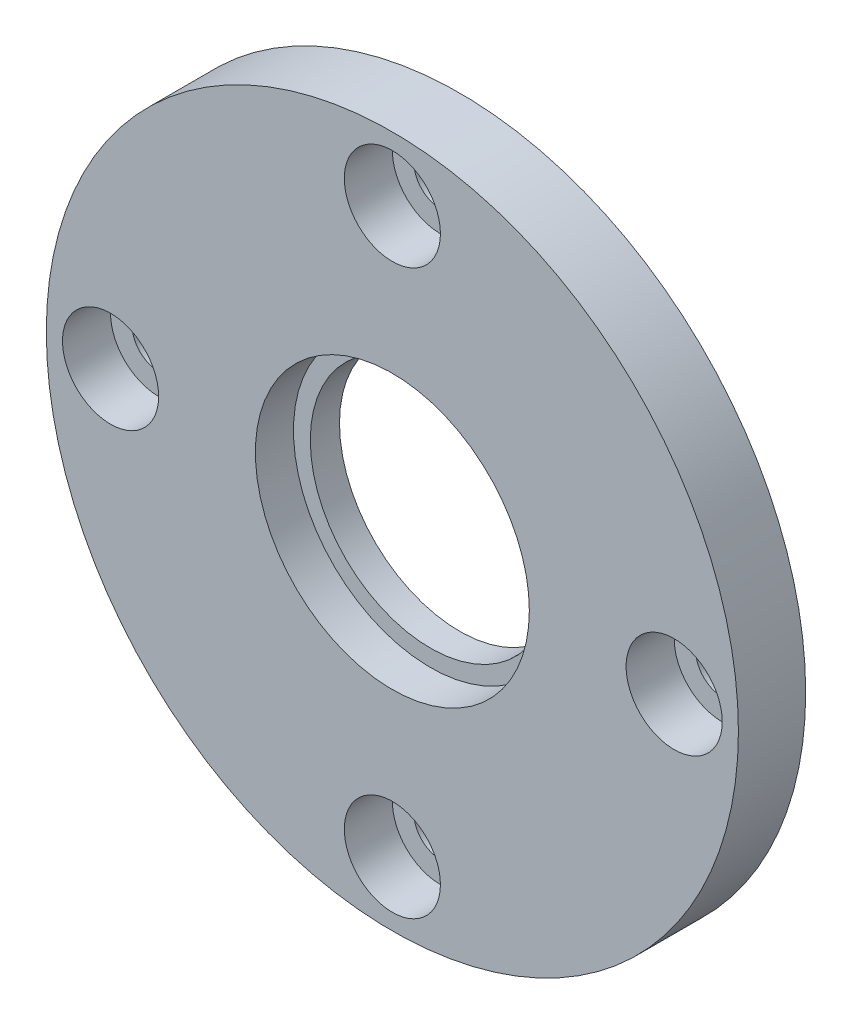
SolidWorks part; units mm, degrees
ref_plane "Front Plane" through (0, 0, 0) normal (0, 0, 1) x (1, 0, 0)
ref_plane "Top Plane" through (0, 0, 0) normal (0, 1, 0) x (1, 0, 0)
ref_plane "Right Plane" through (0, 0, 0) normal (1, 0, 0) x (0, 0, -1)
sketch "Sketch1" plane through (0, 0, 0) normal (1, 0, 0) x (0, 0, -1)
  line L0 (-114.9, -9.5) -> (-144, -9.5)
  line L5 (-1000, 0) -> (49000, 0)
  line L6 (0, -9.5) -> (0, 9.5)
  line L13 (0, 9.5) -> (-53.3, 9.5)
  line L26 (-53.3, 9.5) -> (-53.3, 14)
  line L27 (-53.3, 14) -> (-114.9, 14)
  line L32 (-114.9, 14) -> (-114.9, 9.5)
  line L34 (-160, 7) -> (-160, -7)
  line L36 (-114.9, -9.5) -> (-114.9, -14)
  line L37 (-114.9, -14) -> (-53.3, -14)
  line L38 (-53.3, -14) -> (-53.3, -9.5)
  line L39 (0, -9.5) -> (-53.3, -9.5)
  line L40 (-21.7, 36) -> (-14.7, 36)
  line L41 (-131.5, 22.6312) -> (-114.9, 22.6312)
  line L42 (-131.5, 22.6312) -> (-131.5, -22.6312)
  line L43 (-131.5, -22.6312) -> (-114.9, -22.6312)
  line L44 (-114.9, 22.6312) -> (-114.9, -22.6312)
  line L45 (-131.5, 22.6312) -> (-114.9, -22.6312) construction
  line L46 (-131.5, -22.6312) -> (-114.9, 22.6312) construction
  line L47 (-36.7, 22.6312) -> (-53.3, 22.6312)
  line L48 (-36.7, 22.6312) -> (-36.7, -22.6312)
  line L49 (-36.7, -22.6312) -> (-53.3, -22.6312)
  line L50 (-53.3, 22.6312) -> (-53.3, -22.6312)
  line L51 (-36.7, 22.6312) -> (-53.3, -22.6312) construction
  line L52 (-36.7, -22.6312) -> (-53.3, 22.6312) construction
  line L59 (-14.7, 36) -> (-14.7, -36)
  line L60 (-14.7, -36) -> (-21.7, -36)
  line L61 (-21.7, -22.6312) -> (-26.7, -22.6312)
  line L62 (-26.7, -22.6312) -> (-26.7, -12.6312)
  line L63 (-26.7, -12.6312) -> (-21.7, -12.6312)
  line L64 (-21.7, -12.6312) -> (-21.7, 12.6312)
  line L65 (-21.7, 12.6312) -> (-26.7, 12.6312)
  line L66 (-26.7, 12.6312) -> (-26.7, 22.6312)
  line L67 (-26.7, 22.6312) -> (-21.7, 22.6312)
  line L68 (-21.7, 22.6312) -> (-21.7, 36)
  line L69 (-21.7, -22.6312) -> (-21.7, -36)
  line L71 (-133.659, 36) -> (-22.7, 36)
  line L72 (-133.659, 36) -> (-133.659, -36)
  line L73 (-133.659, -36) -> (-22.7, -36)
  line L74 (-22.7, 36) -> (-22.7, -36)
  line L75 (-133.659, 36) -> (-22.7, -36) construction
  line L76 (-133.659, -36) -> (-22.7, 36) construction
  line L77 (-144, -9.5) -> (-144, -7)
  line L78 (-144, -7) -> (-160, -7)
  line L79 (-114.9, 9.5) -> (-144, 9.5)
  line L80 (-144, 7) -> (-160, 7)
  line L81 (-144, 9.5) -> (-144, 7)
  line L82 (-129.45, 9.5) -> (-129.45, -9.5) construction
  line L83 (-26.65, 9.5) -> (-26.65, -9.5) construction
  line L96 (-133.659, 36) -> (-140.659, 36)
  line L98 (-133.659, -36) -> (-140.659, -36)
  line L99 (-140.659, 36) -> (-140.659, -36)
  line L110 (-133.659, 36) -> (-133.659, -36)
  point P3 (0, 0)
  point P18 (-123.2, 0)
  point P24 (-45, 0)
  point P29 (-78.1795, 0)
  point P48 (-14.7, 29.3156)
  point P58 (0, 0)
  point P70 (-140.659, 29.3156)
revolve "Main_body" add sketch "Sketch1" angle 360 about L5 region at (0, 22.75, 137.159)
sketch "Sketch2" plane through (0, 0, 133.659) normal (0, 0, -1) x (-1, 0, 0)
  circle A1 centre (0, 0) radius 12.5
  dimension "D1" = 25
extrude "Shaft_thru" cut sketch "Sketch2" against normal through all
hole_wizard "CBORE for M5 SHCS1" positions "Sketch3" profile "Sketch4" counterbore size "M5" standard "ANSI Metric" end condition through all
sketch "Sketch3" plane through (0, 0, 140.659) normal (0, 0, 1) x (1, 0, 0)
  point P0 (0, 29.3156)
sketch "Sketch4" plane through (0, 29.3156, 140.659) normal (1, 0, 0) x (0, -1, 0)
  line L0 (0, 0) -> (0, 7)
  line L1 (0, 7) -> (2.75, 7)
  line L3 (2.75, 7) -> (2.75, 5)
  line L4 (2.75, 5) -> (5, 5)
  line L5 (5, 5) -> (5, 0)
  line L7 (5, 0) -> (0, 0)
  line L11 (0, -6.35) -> (0, 107.95) construction
  dimension "Thru Hole Dia." = 5.5
  dimension "Thru Hole Depth" = 7
  dimension "C'Bore Dia." = 10
  dimension "C'Bore Depth" = 5
pattern_circular "CirPattern1" count 4 over 360 about axis through (0, 0, 1000) along (0, 0, -1) of "CBORE for M5 SHCS1"
sketch "Sketch5" plane through (0, 0, 140.659) normal (0, 0, 1) x (1, 0, 0)
  circle A0 centre (0, 0) radius 14.25
  dimension "D1" = 28.5
extrude "seal_seat" cut sketch "Sketch5" against normal blind 3.9624
